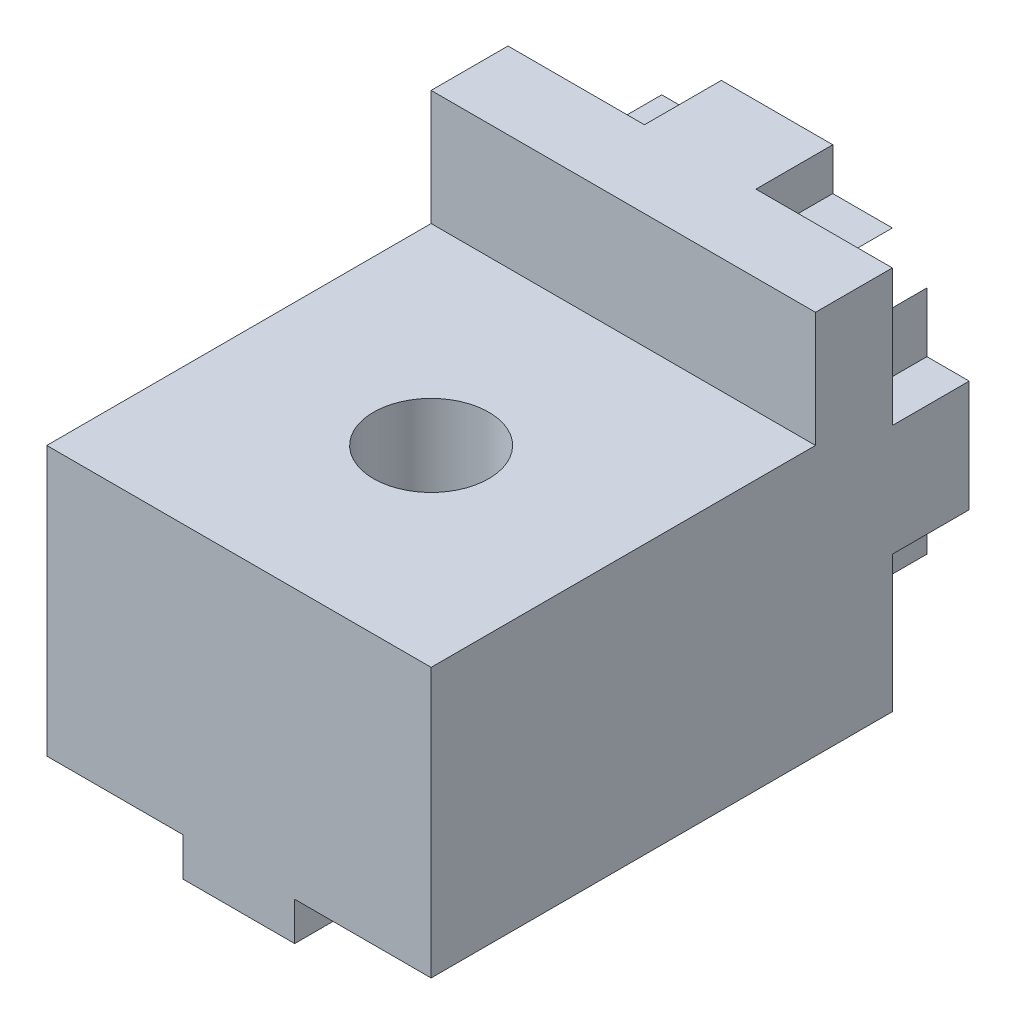
SolidWorks part; units mm, degrees
ref_plane "Front Plane" through (0, 0, 0) normal (0, 0, 1) x (1, 0, 0)
ref_plane "Top Plane" through (0, 0, 0) normal (0, 1, 0) x (1, 0, 0)
ref_plane "Right Plane" through (0, 0, 0) normal (1, 0, 0) x (0, 0, -1)
ref_axis "Axis1" through (0, 0, -1.2) along (0, 0, 1)
sketch "Sketch1" plane through (0, 0, 0) normal (0, 0, 1) x (1, 0, 0)
  line L1 (-5, -5) -> (5, -5)
  line L2 (-5, -5) -> (-5, 5)
  line L3 (-5, 5) -> (5, 5)
  line L4 (5, -5) -> (5, 5)
  line L5 (-5, -5) -> (5, 5) construction
  line L6 (-5, 5) -> (5, -5) construction
  point P0 (0, 0)
  dimension "D1" = 10
  dimension "D2" = 10
extrude "Main" add sketch "Sketch1" along normal blind 12
sketch "Sketch2" plane through (0, 0, 0) normal (0, 0, -1) x (-1, 0, 0)
  line L0 (-5, 1.45) -> (-3.9, 1.45)
  line L1 (-5, -5) -> (-5, 5) construction
  line L2 (-3.9, 1.45) -> (-3.9, 3)
  line L3 (-3.9, -1.45) -> (-5, -1.45)
  line L4 (-5, 1.45) -> (-5, -1.45)
  line L5 (-3.9, 3) -> (-2.1, 0.95)
  line L6 (-2.1, 0.95) -> (-2.1, -0.95)
  line L7 (-2.1, -0.95) -> (-3.9, -3)
  line L8 (-3.9, -3) -> (-3.9, -1.45)
  line L9 (-5, 5) -> (5, 5) construction
  point P5 (-2.1, 0)
  dimension "D1" = 2.9
  dimension "D2" = 1.1
  dimension "D3" = 1.9
  dimension "D4" = 2.1
  dimension "D5" = 2
extrude "AntiRotationSystem" add sketch "Sketch2" along normal blind 2
pattern_circular "CirPattern1" count 4 over 360 about axis through (0, 0, -1.2) along (0, 0, 1) of "AntiRotationSystem"
sketch "Sketch3" plane through (0, 5, 0) normal (0, 1, 0) x (1, 0, 0)
  line L0 (-5, -12) -> (-5, 0) construction
  line L1 (5, -12) -> (-5, -12)
  line L2 (5, -12) -> (5, -2)
  line L3 (5, -2) -> (-5, -2)
  line L4 (-5, -12) -> (-5, -2)
  dimension "D1" = 10
extrude "MakerBeamSquareHoleForScrew" cut sketch "Sketch3" against normal blind 3
sketch "Sketch5" plane through (0, -5, 0) normal (0, -1, 0) x (-1, 0, 0)
  line L0 (5, -12) -> (-5, -12) construction
  line L1 (1.45, 0) -> (-1.45, 0)
  line L2 (1.45, 0) -> (1.45, -12)
  line L3 (1.45, -12) -> (-1.45, -12)
  line L4 (-1.45, 0) -> (-1.45, -12)
  line L5 (0, 1.2) -> (0, -3.2) construction
  line L6 (-1.45, 0) -> (-5, 0) construction
  point P6 (0, -12)
  point P7 (0, 0)
  point P10 (0, 0)
  point P11 (0, 0)
  dimension "D1" = 2.9
extrude "MakerBeamRail" add sketch "Sketch5" along normal blind 1
sketch "Sketch4" plane through (0, 2, 0) normal (0, 1, 0) x (1, 0, 0)
  line L0 (-5, -12) -> (5, -12) construction
  line L1 (0, 1.2) -> (0, -3.2) construction
  circle A0 centre (0, -7) radius 1.5
  dimension "D1" = 3
  dimension "D2" = 5
extrude "VerticalMakerBeamHole" cut sketch "Sketch4" against normal through all
